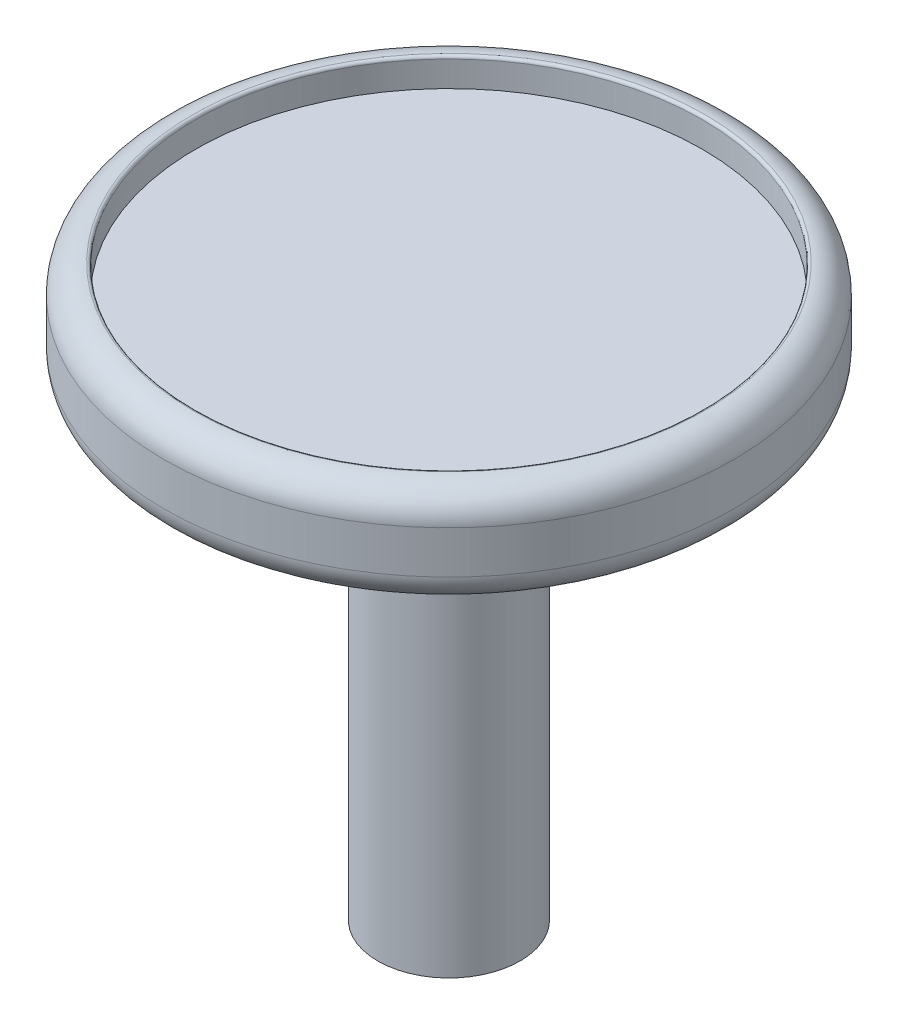
SolidWorks part; units mm, degrees
ref_plane "Front Plane" through (0, 0, 0) normal (0, 0, 1) x (1, 0, 0)
ref_plane "Top Plane" through (0, 0, 0) normal (0, 1, 0) x (1, 0, 0)
ref_plane "Right Plane" through (0, 0, 0) normal (1, 0, 0) x (0, 0, -1)
sketch "Sketch2" plane through (0, 0, 0) normal (0, 1, 0) x (1, 0, 0)
  line L1 (-1.025, 0.65) -> (1.025, 0.65)
  line L2 (-1.025, 0.65) -> (-1.025, -0.65)
  line L3 (-1.025, -0.65) -> (1.025, -0.65)
  line L4 (1.025, 0.65) -> (1.025, -0.65)
  line L5 (-1.025, 0.65) -> (1.025, -0.65) construction
  line L6 (-1.025, -0.65) -> (1.025, 0.65) construction
  circle A0 centre (0, 0) radius 2.5
  dimension "D1" = 5
  dimension "D2" = 1.3
  dimension "D3" = 2.05
extrude "Boss-Extrude1" add sketch "Sketch2" along normal mid plane 20
fillet "Fillet1" radius 1 1 edges at (0, 10, 2.5)
sketch "Sketch3" plane through (0, 10, 0) normal (0, 1, 0) x (1, 0, 0)
  line L0 (1.025, -0.65) -> (1.025, 0.65) construction
  line L1 (-1.025, -0.65) -> (1.025, -0.65) construction
  line L2 (-1.025, 0.65) -> (-1.025, -0.65) construction
  line L3 (1.025, 0.65) -> (-1.025, 0.65) construction
  line L4 (1.025, -0.65) -> (1.025, 0.65)
  line L5 (-1.025, -0.65) -> (1.025, -0.65)
  line L6 (-1.025, 0.65) -> (-1.025, -0.65)
  line L7 (1.025, 0.65) -> (-1.025, 0.65)
extrude "Boss-Extrude5" add sketch "Sketch3" against normal blind 16
sketch "Sketch4" plane through (0, 10, 0) normal (0, 1, 0) x (1, 0, 0)
  circle A0 centre (0, 0) radius 10
  circle A1 centre (0, 0) radius 9
  circle A2 centre (0, 0) radius 8.9
  dimension "D1" = 20
  dimension "D2" = 18
  dimension "D3" = 0.1
extrude "Thumb Stick" add sketch "Sketch4" against normal blind 3.5 contours A0
fillet "Fillet2" radius 1 1 edges at (0, 6.5, 10)
fillet "Fillet3" radius 1 1 edges at (0, 10, 10)
extrude "Cut-Extrude1" cut sketch "Sketch4<4>" against normal blind 1 contours A2
sketch "Sketch4<4>" plane through (0, 10, 0) normal (0, 1, 0) x (1, 0, 0) same geometry as "Sketch4"
fillet "Fillet5" radius 0.1 1 edges at (0, 10, 8.9)
